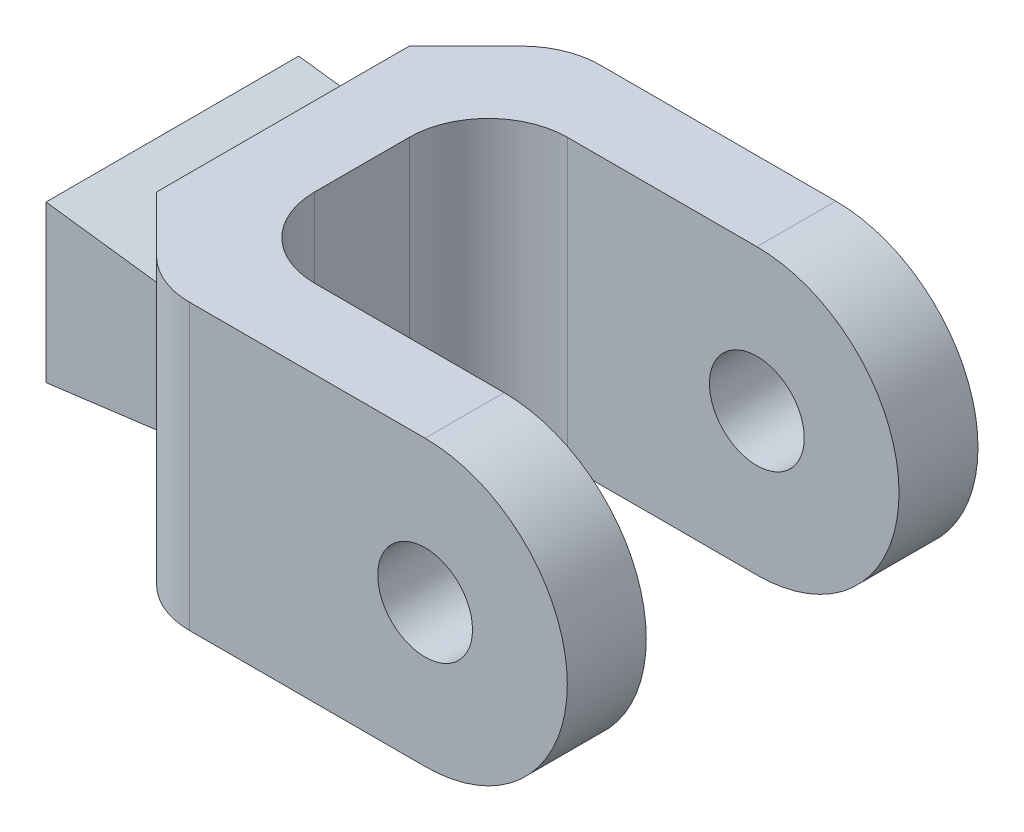
SolidWorks part; units mm, degrees
ref_plane "Front Plane" through (0, 0, 0) normal (0, 0, 1) x (1, 0, 0)
ref_plane "Top Plane" through (0, 0, 0) normal (0, 1, 0) x (1, 0, 0)
ref_plane "Right Plane" through (0, 0, 0) normal (1, 0, 0) x (0, 0, -1)
sketch "Sketch1" plane through (0, 0, 0) normal (0, 0, 1) x (1, 0, 0)
  line L0 (-2.2687, 0) -> (4.5375, 0) construction
  line L4 (-1.75, -2.475) -> (-1.75, 2.475)
  line L5 (1.4583, -2.0625) -> (-1.75, 2.475) construction
  line L6 (1.4583, 2.0625) -> (-1.75, -2.475) construction
  line L7 (-1.75, -2.475) -> (1.75, -2.025)
  line L8 (-1.75, 2.475) -> (1.75, 2.025)
  line L21 (1.75, 2.025) -> (1.75, 4.5)
  line L22 (4.25, -4.5) -> (1.75, -4.5)
  line L25 (4.25, -4.5) -> (4.25, 4.5)
  line L26 (4.25, 4.5) -> (1.75, 4.5)
  line L27 (1.75, -4.5) -> (1.75, -2.025)
  line L28 (4.25, -4.5) -> (1.75, 4.5) construction
  line L29 (4.25, 4.5) -> (1.75, -4.5) construction
  point P0 (0, 0)
  point P2 (3, 0)
  point P3 (3, 0)
  point P6 (1.75, 2.025)
  point P9 (1.75, -2.025)
  dimension "D1" = 4.95
  dimension "D2" = 2.5
  dimension "D3" = 9
extrude "Boss-Extrude1" add sketch "Sketch1" along normal blind 8 contours L8 L21 L26 L25 L22 L27 L7 L4
sketch "Sketch2" plane through (0, 0, 0) normal (0, 0, 1) x (1, 0, 0)
  line L0 (-1.75, 0) -> (25.7432, 0) construction
  line L1 (-1.75, -2.475) -> (-1.75, 2.475) construction
  line L3 (12.75, -4.5) -> (1.75, -4.5)
  line L5 (12.75, 4.5) -> (1.75, 4.5)
  line L6 (1.75, -4.5) -> (1.75, 4.5)
  line L7 (15.7356, -3.3669) -> (1.75, 4.5) construction
  line L8 (15.7356, 3.3669) -> (1.75, -4.5) construction
  line L11 (1.75, -4.5) -> (1.75, -2.025) construction
  arc A0 (12.75, -4.5) -> (12.75, 4.5) centre (12.75, 0) ccw
  circle A1 centre (12.75, 0) radius 1.5
  point P5 (9.75, 0)
  point P7 (17.25, 0)
  dimension "D3" = 3
  dimension "D1" = 15.5
  dimension "D2" = 9
extrude "Boss-Extrude3" add sketch "Sketch2" against normal blind 2.5
sketch "Sketch5" plane through (0, 0, 0) normal (0, 1, 0) x (1, 0, 0)
  line L0 (4.25, 0) -> (4.25, 4.091) construction
  line L1 (12.75, 2.5) -> (1.75, 2.5) construction
  line L2 (1.75, 0) -> (4.25, 2.5)
  line L3 (4.25, 2.5) -> (1.75, 2.5)
  line L4 (1.75, 2.5) -> (1.75, 0)
  point P3 (4.25, 2.5)
extrude "Cut-Extrude2" cut sketch "Sketch5" against normal through all and the other way through all
fillet "Fillet5" radius 2.5 1 edges at (4.25, 0, 0)
fillet "Fillet6" radius 2.5 1 edges at (4.25, 0, -2.5)
ref_plane "Plane1" through (0, 0, 4) normal (0, 0, -1) x (-1, 0, 0)
mirror "Mirror2" about plane through (0, 0, 4) normal (0, 0, -1) of "Cut-Extrude2", "Fillet6", "Fillet5", "Boss-Extrude3"
